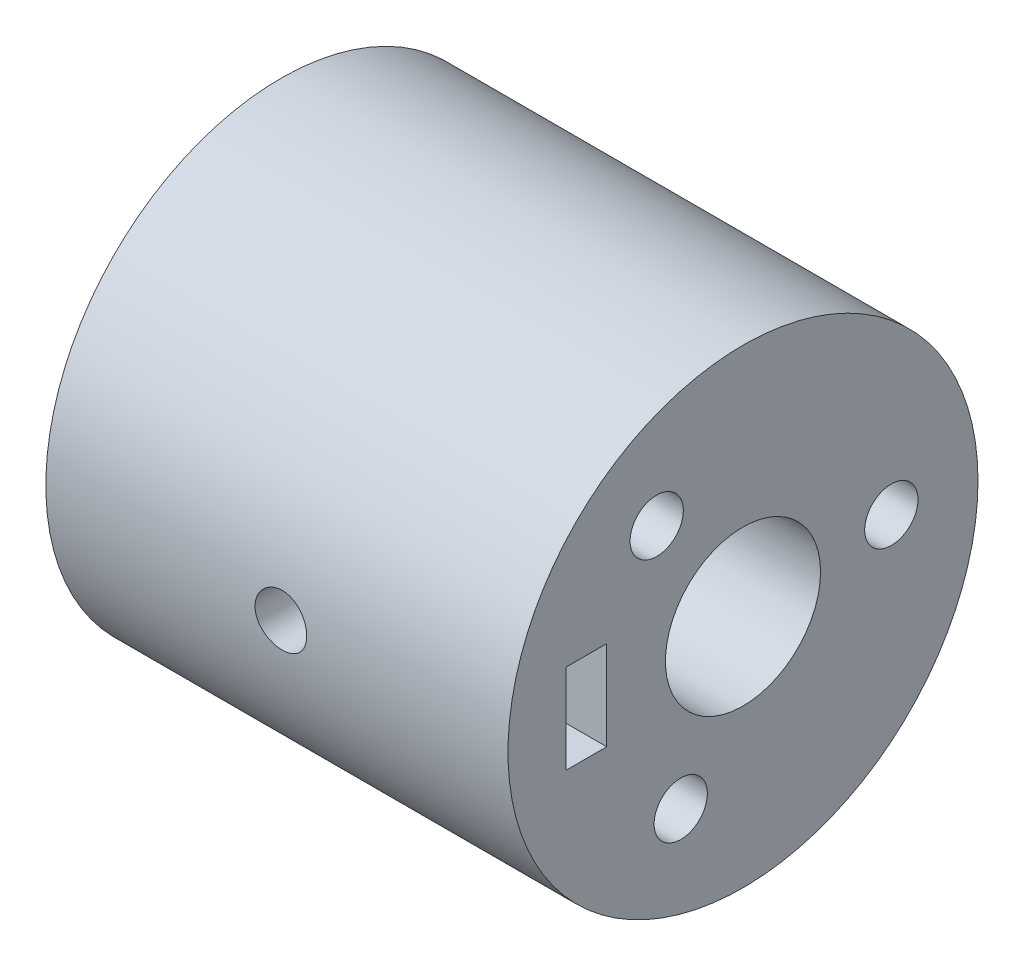
SolidWorks part; units mm, degrees
ref_plane "Front Plane" through (0, 0, 0) normal (1, 0, 0) x (0, 1, 0)
ref_plane "Top Plane" through (0, 0, 0) normal (0, 0, 1) x (0, 1, 0)
ref_plane "Right Plane" through (0, 0, 0) normal (0, 1, 0) x (-1, 0, 0)
sketch "Sketch1" plane through (0, 0, 0) normal (1, 0, 0) x (0, 1, 0)
  circle A0 centre (0, 0) radius 15
  dimension "D1" = 30
extrude "Boss-Extrude1" add sketch "Sketch1" along normal blind 29.5
sketch "Sketch2" plane through (29.5, 0, 0) normal (1, 0, 0) x (0, 1, 0)
  circle A0 centre (0, 0) radius 4.95
  circle A1 centre (-8.6395, 3.9749) radius 1.7
  circle A2 centre (7.7689, 5.5095) radius 1.7
  circle A3 centre (0.8938, -9.4679) radius 1.7
  dimension "D1" = 9.9
  dimension "D2" = 16.48
  dimension "D3" = 3.4
  dimension "D4" = 16.48
  dimension "D5" = 3.4
  dimension "D6" = 9.51
  dimension "D7" = 3.4
  dimension "D8" = 9.51
  dimension "D9" = 16.48
extrude "Cut-Extrude1" cut sketch "Sketch2" against normal blind 34
ref_plane "Plane1" through (0, 0, 15) normal (0, 0, 1) x (0, 1, 0)
sketch "Sketch3" plane through (0, 0, 15) normal (0, 0, 1) x (0, 1, 0)
  line L0 (15, 0) -> (-15, 0) construction
  line L1 (15, -29.5) -> (15, 0) construction
  circle A0 centre (0, -15) radius 1.65
  dimension "D1" = 3.3
  dimension "D2" = 15
  dimension "D3" = 15
extrude "Cut-Extrude2" cut sketch "Sketch3" against normal blind 12
ref_plane "Plane2" through (0, 0, 10) normal (0, 0, 1) x (0, 1, 0)
sketch "Sketch4" plane through (0, 0, 10) normal (0, 0, 1) x (0, 1, 0)
  line L1 (-2.85, -16.6454) -> (0, -18.2909)
  line L2 (0, -18.2909) -> (2.85, -16.6454)
  line L3 (2.85, -16.6454) -> (2.85, -13.3546)
  line L4 (2.85, -13.3546) -> (0, -11.7091)
  line L5 (0, -11.7091) -> (-2.85, -13.3546)
  line L6 (-2.85, -13.3546) -> (-2.85, -16.6454)
  circle A0 centre (0, -15) radius 2.85 construction
  point P1 (0, -11.7091)
  dimension "D2" = 5.7
extrude "Cut-Extrude3" cut sketch "Sketch4" against normal blind 1.3 and the other way blind 1.3
sketch "Sketch5" plane through (29.5, 0, 0) normal (1, 0, 0) x (0, 1, 0)
  line L0 (2.85, 10) -> (-2.85, 10) construction
  line L1 (2.85, 8.7) -> (-2.85, 8.7)
  line L2 (2.85, 8.7) -> (2.85, 11.3)
  line L3 (2.85, 11.3) -> (-2.85, 11.3)
  line L4 (-2.85, 8.7) -> (-2.85, 11.3)
  line L5 (2.85, 8.7) -> (-2.85, 11.3) construction
  line L6 (2.85, 11.3) -> (-2.85, 8.7) construction
  point P0 (0, 10)
  dimension "D1" = 5.7
  dimension "D2" = 2.6
extrude "Cut-Extrude4" cut sketch "Sketch5" against normal blind 16
